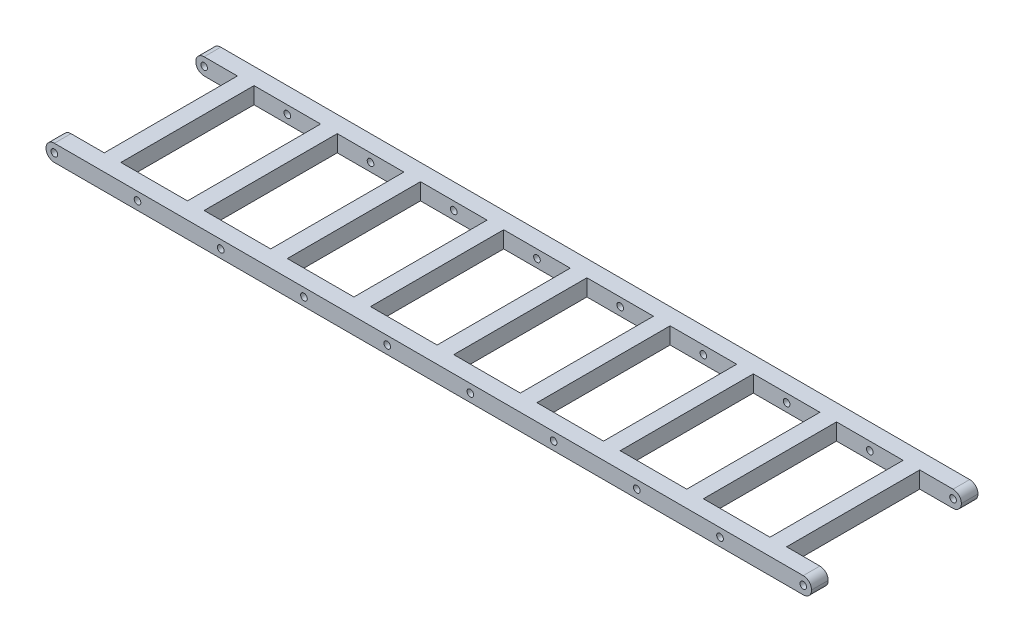
SolidWorks part; units mm, degrees
ref_plane "Front Plane" through (0, 0, 0) normal (0, 0, 1) x (1, 0, 0)
ref_plane "Top Plane" through (0, 0, 0) normal (0, 1, 0) x (1, 0, 0)
ref_plane "Right Plane" through (0, 0, 0) normal (1, 0, 0) x (0, 0, -1)
sketch "Sketch1" plane through (0, 0, 0) normal (0, 1, 0) x (1, 0, 0)
  line L0 (-146.05, 25.4) -> (-130.175, 25.4)
  line L1 (-146.05, 31.75) -> (146.05, 31.75)
  line L2 (-146.05, 31.75) -> (-146.05, 25.4)
  line L3 (-146.05, -31.75) -> (146.05, -31.75)
  line L4 (146.05, 31.75) -> (146.05, 25.4)
  line L5 (-146.05, 31.75) -> (146.05, -31.75) construction
  line L6 (-146.05, -31.75) -> (146.05, 31.75) construction
  line L8 (-146.05, -25.4) -> (-130.175, -25.4)
  line L10 (0, 31.75) -> (0, -31.75) construction
  line L11 (-3.175, 25.4) -> (-3.175, -25.4)
  line L12 (130.175, 25.4) -> (130.175, -25.4)
  line L13 (123.825, 25.4) -> (123.825, -25.4)
  line L14 (-3.175, 31.75) -> (-3.175, -31.75) construction
  line L15 (-28.575, 25.4) -> (-28.575, -25.4)
  line L16 (-34.925, 25.4) -> (-34.925, -25.4)
  line L17 (-60.325, 25.4) -> (-60.325, -25.4)
  line L18 (-66.675, 25.4) -> (-66.675, -25.4)
  line L19 (-92.075, 25.4) -> (-92.075, -25.4)
  line L20 (-98.425, 25.4) -> (-98.425, -25.4)
  line L21 (-123.825, 25.4) -> (-123.825, -25.4)
  line L22 (-130.175, 25.4) -> (-130.175, -25.4)
  line L23 (-146.05, -25.4) -> (-146.05, -31.75)
  line L24 (146.05, -25.4) -> (146.05, -31.75)
  line L25 (98.425, 25.4) -> (98.425, -25.4)
  line L26 (92.075, 25.4) -> (92.075, -25.4)
  line L27 (66.675, 25.4) -> (66.675, -25.4)
  line L28 (60.325, 25.4) -> (60.325, -25.4)
  line L29 (34.925, 25.4) -> (34.925, -25.4)
  line L30 (28.575, 25.4) -> (28.575, -25.4)
  line L31 (3.175, 25.4) -> (3.175, -25.4)
  line L32 (-123.825, 25.4) -> (-98.425, 25.4)
  line L33 (-123.825, -25.4) -> (-98.425, -25.4)
  line L34 (-92.075, 25.4) -> (-66.675, 25.4)
  line L35 (-92.075, -25.4) -> (-66.675, -25.4)
  line L36 (-28.575, -25.4) -> (-3.175, -25.4)
  line L37 (-60.325, 25.4) -> (-34.925, 25.4)
  line L38 (-28.575, 25.4) -> (-3.175, 25.4)
  line L39 (3.175, 25.4) -> (28.575, 25.4)
  line L40 (3.175, -25.4) -> (28.575, -25.4)
  line L41 (34.925, -25.4) -> (60.325, -25.4)
  line L42 (34.925, 25.4) -> (60.325, 25.4)
  line L43 (66.675, 25.4) -> (92.075, 25.4)
  line L44 (66.675, -25.4) -> (92.075, -25.4)
  line L45 (98.425, 25.4) -> (123.825, 25.4)
  line L46 (98.425, -25.4) -> (123.825, -25.4)
  line L47 (130.175, -25.4) -> (146.05, -25.4)
  line L48 (130.175, 25.4) -> (146.05, 25.4)
  line L49 (-60.325, -25.4) -> (-34.925, -25.4)
  point P0 (0, 0)
  dimension "D1" = 63.5
  dimension "D2" = 292.1
  dimension "D4" = 3.175
  dimension "D3" = 6.35
  dimension "D14" = 6.35
  dimension "D6" = 25.4
  dimension "D7" = 6.35
  dimension "D8" = 25.4
  dimension "D9" = 6.35
  dimension "D10" = 25.4
  dimension "D11" = 6.35
  dimension "D12" = 25.4
  dimension "D13" = 6.35
extrude "Boss-Extrude1" add sketch "Sketch1" against normal blind 6.35
sketch "Sketch2" plane through (0, 0, 31.75) normal (0, 0, 1) x (1, 0, 0)
  line L0 (-142.875, 0) -> (-142.875, -6.35) construction
  line L1 (0, 0) -> (0, -6.35) construction
  line L2 (-123.825, 0) -> (-98.425, 0) construction
  line L3 (-123.825, 0) -> (-98.425, 0)
  line L4 (146.05, 0) -> (-146.05, 0)
  line L5 (-146.05, 0) -> (-146.05, -6.35)
  line L6 (-146.05, -6.35) -> (146.05, -6.35)
  line L7 (146.05, -6.35) -> (146.05, 0)
  line L8 (146.05, 0) -> (-146.05, 0)
  line L9 (-146.05, 0) -> (-146.05, -6.35)
  line L10 (-146.05, -6.35) -> (146.05, -6.35)
  line L11 (146.05, -6.35) -> (146.05, 0)
  circle A0 centre (-142.875, -3.175) radius 3.81
  circle A1 centre (-111.125, -3.175) radius 3.81
  circle A2 centre (-15.875, -3.175) radius 3.81
  circle A3 centre (-79.375, -3.175) radius 3.81
  circle A4 centre (-47.625, -3.175) radius 3.81
  circle A5 centre (-142.875, -3.175) radius 1.27
  circle A6 centre (-111.125, -3.175) radius 1.27
  circle A7 centre (-79.375, -3.175) radius 1.27
  circle A8 centre (-47.625, -3.175) radius 1.27
  circle A9 centre (-15.875, -3.175) radius 1.27
  circle A10 centre (15.875, -3.175) radius 1.27
  circle A11 centre (47.625, -3.175) radius 1.27
  circle A12 centre (79.375, -3.175) radius 1.27
  circle A13 centre (111.125, -3.175) radius 1.27
  circle A14 centre (142.875, -3.175) radius 1.27
  point P4 (-146.05, -3.175)
  point P15 (-111.125, 0)
  dimension "D1" = 7.62
  dimension "D4" = 7.62
  dimension "D5" = 7.62
  dimension "D6" = 7.62
  dimension "D7" = 7.62
  dimension "D11" = 2.54
  dimension "D12" = 2.54
  dimension "D13" = 2.54
  dimension "D14" = 2.54
  dimension "D15" = 2.54
  dimension "D8" = 31.75
  dimension "D9" = 31.75
  dimension "D10" = 31.75
  dimension "D2" = 0
  dimension "D3" = 3.175
extrude "Cut-Extrude1" cut sketch "Sketch2" against normal up to surface (63.5 mm away) contours A5 | A6 | A7 | A8 | A9 | A10 | A11 | A12 | A13 | A14 region at (-142.875, -3.175, 31.75) region at (-111.125, -3.175, 31.75) region at (-79.375, -3.175, 31.75) region at (-47.625, -3.175, 31.75) region at (-15.875, -3.175, 31.75) region at (15.875, -3.175, 31.75) region at (47.625, -3.175, 31.75) region at (79.375, -3.175, 31.75) region at (111.125, -3.175, 31.75) region at (142.875, -3.175, 31.75) up to face at (0, -3.175, -31.75)
fillet "Fillet2" radius 3.175 8 edges at (-146.05, -6.35, 28.575) (-146.05, 0, 28.575) (-146.05, -6.35, -28.575) (-146.05, 0, -28.575) (146.05, -6.35, -28.575) (146.05, 0, -28.575) (146.05, -6.35, 28.575) (146.05, 0, 28.575)
